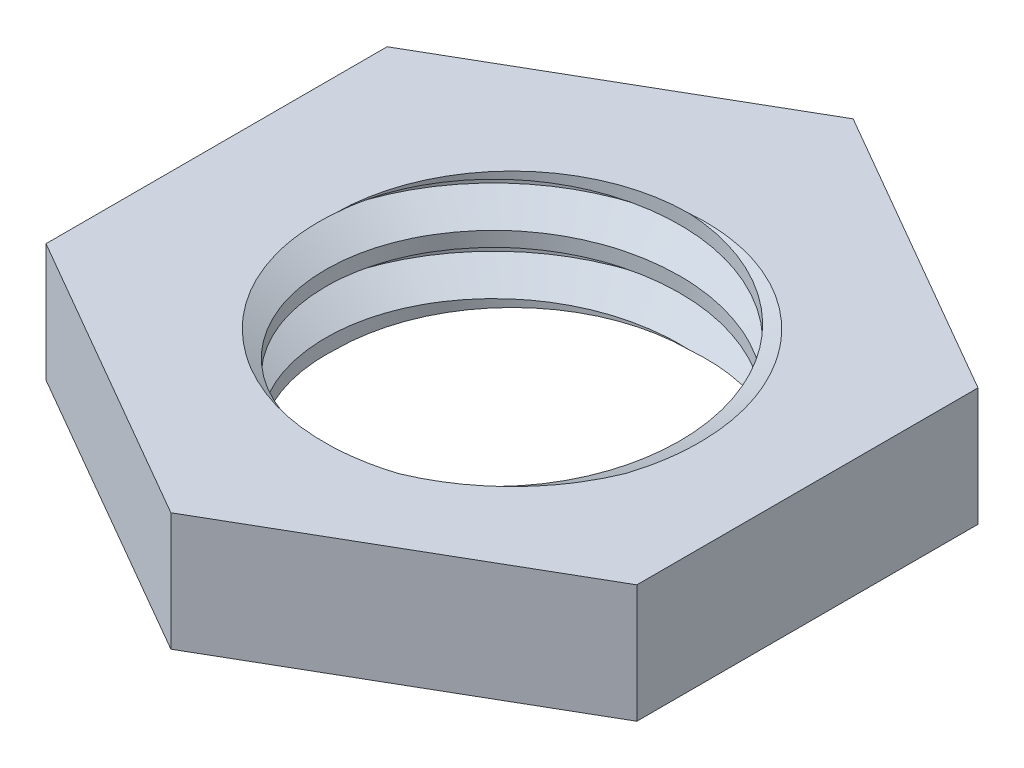
SolidWorks part; units mm, degrees
ref_plane "Спереди" through (0, 0, 0) normal (0, 0, 1) x (1, 0, 0)
ref_plane "Сверху" through (0, 0, 0) normal (0, 1, 0) x (1, 0, 0)
ref_plane "Справа" through (0, 0, 0) normal (1, 0, 0) x (0, 0, -1)
sketch "Эскиз1" plane through (0, 0, 0) normal (0, 1, 0) x (1, 0, 0)
  line L0 (-5, -2.8868) -> (-5, 2.8868)
  line L1 (-5, 2.8868) -> (0, 5.7735)
  line L2 (0, 5.7735) -> (5, 2.8868)
  line L3 (5, 2.8868) -> (5, -2.8868)
  line L4 (5, -2.8868) -> (0, -5.7735)
  line L5 (0, -5.7735) -> (-5, -2.8868)
  circle A1 centre (0, 0) radius 2.5
  point P17 (0, 0)
  dimension "D1" = 5
  dimension "D2" = 5
  dimension "D4" = 11.547
  dimension "D5" = 2.8868
  dimension "D3" = 6
extrude "Бобышка-Вытянуть1" add sketch "Эскиз1" along normal blind 2
hole_wizard "Сверление под метчик M7x1.02" positions "Эскиз6" profile "Эскиз7" hole size "M7x1.0" standard "ISO"
sketch "Эскиз6" plane through (0, 2, 0) normal (0, 1, 0) x (1, 0, 0)
  point P0 (0, 0)
sketch "Эскиз7" plane through (0, 2, 0) normal (1, 0, 0) x (0, 0, 1)
  line L0 (0, 0) -> (0, 11.8026)
  line L1 (0, 11.8026) -> (3, 10)
  line L2 (3, 10) -> (3, 0)
  line L5 (3, 0) -> (0, 0)
  line L10 (0, 11.8026) -> (-3, 10) construction
  line L11 (0, -6.35) -> (0, 107.95) construction
  dimension "Диаметр отверстия" = 6
  dimension "Глубина отверстия" = 10
  dimension "Угол заточки сверла" = 118
thread "Резьба2" pitch 1 method cut profile "Профиль резьбы2" start angle 0, offset 1, length 5, pitch 1, diameter 6
ref_plane "Плоскость2" through (-3, 3, 0) normal (0, 0, 1) x (-1, 0, 0)
sketch "Профиль резьбы2" plane through (-3, 3, 0) normal (0, 0, 1) x (-1, 0, 0)
  line L0 (0, 0) -> (0, 1) construction
  line L1 (0, 0) -> (0.5413, 0.3125)
  line L2 (0.5413, 0.3125) -> (0.5413, 0.4375)
  line L3 (0.5413, 0.4375) -> (0, 0.75)
  line L4 (0.5413, 0.375) -> (0, 0.375) construction
  line L11 (0, 0) -> (0, 0.75)
  point P2 (0, 0)
  dimension "Pitch" = 1
  dimension "Profile_Angle" = 60
  dimension "Profile_Land" = 0.125
  dimension "Profile_Height" = 0.5413
